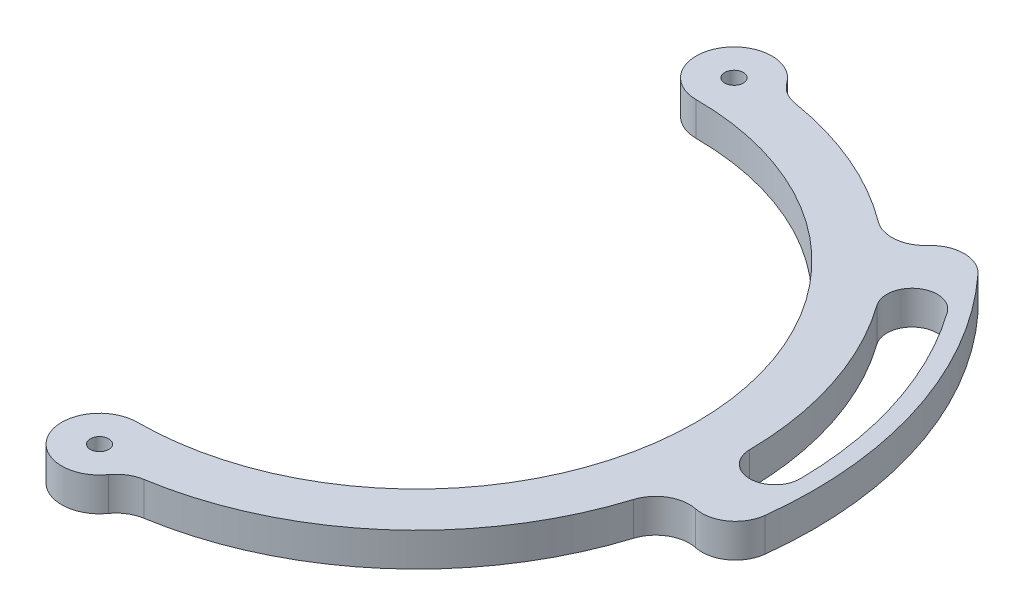
SolidWorks part; units mm, degrees
ref_plane "Front Plane" through (0, 0, 0) normal (0, 0, 1) x (1, 0, 0)
ref_plane "Top Plane" through (0, 0, 0) normal (0, 1, 0) x (1, 0, 0)
ref_plane "Right Plane" through (0, 0, 0) normal (1, 0, 0) x (0, 0, -1)
sketch "Sketch1" plane through (0, 0, 0) normal (0, 1, 0) x (1, 0, 0)
  line L0 (0, 98.05) -> (0, -98.05) construction
  line L1 (78.9909, 87.7282) -> (0, 0) construction
  line L2 (115.4703, -24.544) -> (0, 0) construction
  line L3 (-970, 94.3) -> (49030, 94.3) construction
  line L4 (0, 0) -> (112.2722, 36.4795) construction
  line L5 (85.9299, 61.2932) -> (0, 0) construction
  line L6 (78.9909, 87.7282) -> (65.6083, 72.8654)
  line L7 (115.4703, -24.544) -> (95.9074, -20.3857)
  line L8 (0, 0) -> (-69.7065, 0) construction
  line L9 (-168.2084, 94.3) -> (-168.2084, -94.3) construction
  line L10 (-970, -94.3) -> (49030, -94.3) construction
  arc A0 (0, -83.05) -> (0, 83.05) centre (0, 0) ccw
  arc A1 (10.799, -97.4535) -> (95.9074, -20.3857) centre (0, 0) ccw
  circle A2 centre (0, 0) radius 98.05 construction
  circle A3 centre (0, 0) radius 83.05 construction
  circle A6 centre (0, 0) radius 118.05 construction
  arc A7 (78.9909, 87.7282) -> (115.4703, -24.544) centre (0, 0) cw
  circle A8 centre (0, 0) radius 105.55 construction
  arc A9 (85.9299, 61.2932) -> (105.546, 0.9211) centre (0, 0) cw construction
  arc A10 (113.0457, 0.9865) -> (92.0358, 65.6485) centre (0, 0) ccw
  arc A11 (98.0463, 0.8556) -> (79.824, 56.9379) centre (0, 0) ccw
  arc A12 (98.0463, 0.8556) -> (113.0457, 0.9865) centre (105.546, 0.9211) ccw
  arc A13 (92.0358, 65.6485) -> (79.824, 56.9379) centre (85.9299, 61.2932) ccw
  arc A14 (65.6083, 72.8654) -> (10.799, 97.4535) centre (0, 0) ccw
  arc A15 (10.799, -97.4535) -> (10.799, 97.4535) centre (0, 0) ccw
  arc A16 (0, 83.05) -> (0, 98.05) centre (0, 90.55) cw construction
  arc A17 (0, -98.05) -> (0, -83.05) centre (0, -90.55) cw construction
  arc A18 (10.799, -97.4535) -> (7.8734, -102.3357) centre (0, -94.3) cw
  arc A19 (10.799, 97.4535) -> (0, 83.05) centre (0, 94.3) ccw
  arc A21 (10.799, -97.4535) -> (0, -83.05) centre (0, -94.3) cw
  arc A22 (-10.4017, -102.3357) -> (10.4017, -102.3357) centre (0, -98.05) cw construction
  point P10 (-168.2084, 0)
  point P12 (0, 90.55)
  point P13 (0, -90.55)
  point P15 (0, 0)
  point P22 (100.384, 32.6167)
  point P40 (0, -94.3)
  point P41 (0, 0)
  point P42 (0, 94.3)
  dimension "D2" = 166.1
  dimension "D1" = 11.25
  dimension "D4" = 60
  dimension "D7" = 15
  dimension "D3" = 5
  dimension "D6" = 17.5
  dimension "D5" = 72
  dimension "D9" = 188.6
  dimension "D8" = 15
extrude "Boss-Extrude1" add sketch "Sketch1" along normal mid plane 10 contours A15 L7 A7 L6 A13 A10 A12 | A1 A15 A11 A14 A0 region at (111.0937, 0, -36.0965) region at (71.3774, 0, -63.7068)
hole_wizard "M5 Clearance Hole1" positions "Sketch2" profile "Sketch3" hole size "M5" standard "ANSI Metric" end condition through all
sketch "Sketch2" plane through (0, 5, 0) normal (0, 1, 0) x (1, 0, 0)
  point P22 (0, -94.3)
  point P26 (0, 94.3)
  point P30 (0, 0)
  point P31 (0, 0)
sketch "Sketch3" plane through (0, 5, 94.3) normal (1, 0, 0) x (0, 0, 1)
  line L0 (0, 0) -> (0, 10)
  line L1 (0, 10) -> (2.75, 10)
  line L2 (2.75, 10) -> (2.75, 0)
  line L5 (2.75, 0) -> (0, 0)
  line L11 (0, -6.35) -> (0, 107.95) construction
  dimension "Thru Hole Dia." = 5.5
  dimension "Thru Hole Depth" = 10
fillet "Fillet1" radius 10 6 edges at (78.9909, 0, -87.7282) (115.4703, 0, 24.544) (65.6083, 0, -72.8654) (95.9074, 0, 20.3857) (10.799, 0, 97.4535) (10.799, 0, -97.4535)
equation "\"D2@Sketch1\"=152.40 + (6.35*2) + 1"
